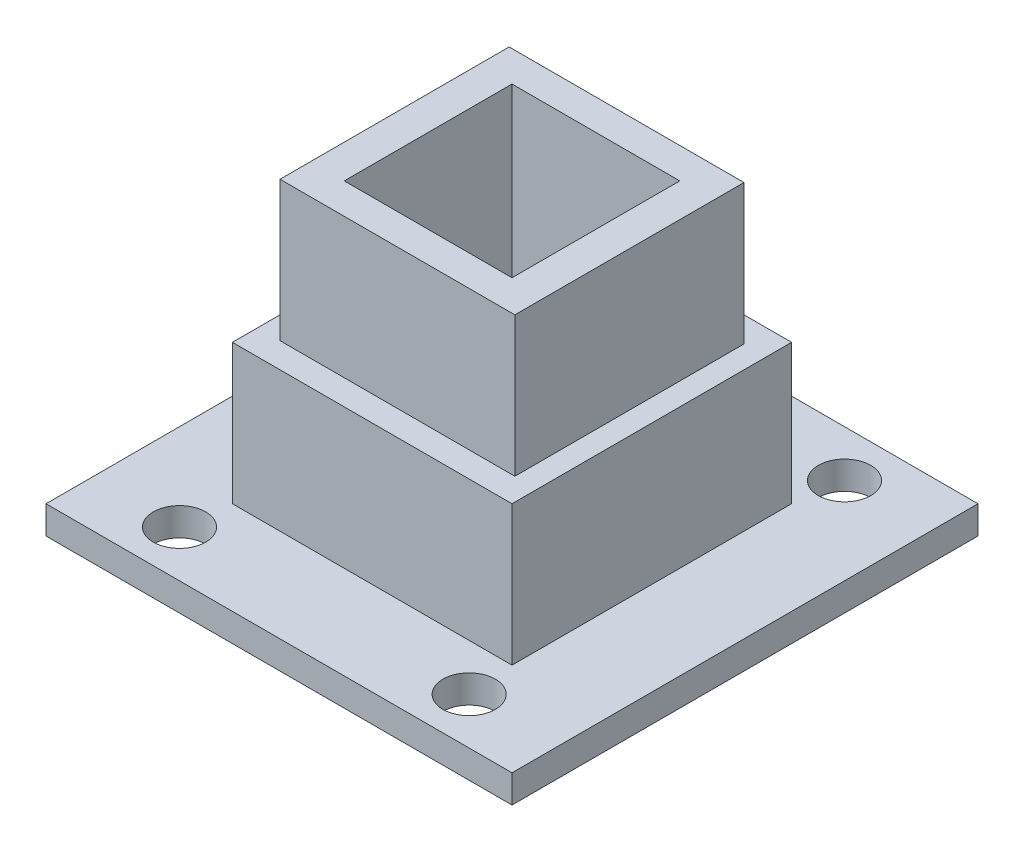
SolidWorks part; units mm, degrees
ref_plane "Alzado" through (0, 0, 0) normal (0, 0, 1) x (1, 0, 0)
ref_plane "Planta" through (0, 0, 0) normal (0, 1, 0) x (1, 0, 0)
ref_plane "Vista lateral" through (0, 0, 0) normal (1, 0, 0) x (0, 0, -1)
sketch "Croquis1" plane through (0, 0, 0) normal (0, 1, 0) x (1, 0, 0)
  line L1 (-25, 25) -> (25, 25)
  line L2 (-25, 25) -> (-25, -25)
  line L3 (-25, -25) -> (25, -25)
  line L4 (25, 25) -> (25, -25)
  line L5 (-25, 25) -> (25, -25) construction
  line L6 (-25, -25) -> (25, 25) construction
  point P0 (0, 0)
  dimension "D1" = 50
  dimension "D2" = 50
extrude "Saliente-Extruir1" add sketch "Croquis1" along normal blind 3
sketch "Croquis2" plane through (0, 3, 0) normal (0, 1, 0) x (1, 0, 0)
  line L1 (-15, 15) -> (15, 15)
  line L2 (-15, 15) -> (-15, -15)
  line L3 (-15, -15) -> (15, -15)
  line L4 (15, 15) -> (15, -15)
  line L5 (-15, 15) -> (15, -15) construction
  line L6 (-15, -15) -> (15, 15) construction
  line L7 (-9, 9) -> (9, 9)
  line L8 (-9, 9) -> (-9, -9)
  line L9 (-9, -9) -> (9, -9)
  line L10 (9, 9) -> (9, -9)
  line L11 (-9, 9) -> (9, -9) construction
  line L12 (-9, -9) -> (9, 9) construction
  point P0 (0, 0)
  point P6 (0, 0)
  dimension "D1" = 30
  dimension "D2" = 30
  dimension "D3" = 6
extrude "Saliente-Extruir2" add sketch "Croquis2" along normal blind 30
sketch "Croquis3" plane through (0, 3, 0) normal (0, 1, 0) x (1, 0, 0)
  line L0 (25, -20) -> (-25, -20) construction
  line L1 (25, -25) -> (25, 25) construction
  line L2 (-25, 25) -> (-25, -25) construction
  line L3 (25, 20) -> (-25, 20) construction
  line L4 (0, -25) -> (0, -15) construction
  line L5 (-25, -25) -> (25, -25) construction
  line L6 (-15, -15) -> (15, -15) construction
  line L7 (0, 15) -> (0, 25) construction
  line L8 (15, 15) -> (-15, 15) construction
  line L9 (25, 25) -> (-25, 25) construction
  line L10 (15.6762, -25) -> (15.6762, 25) construction
  line L11 (-15.6762, -25) -> (-15.6762, 25) construction
  circle A0 centre (15.4054, -20) radius 2.8139
  circle A1 centre (-15.6762, -20) radius 2.8139
  circle A2 centre (15.6762, 20) radius 2.8139
  circle A3 centre (-15.6762, 20) radius 2.8139
  point P22 (0, -20)
  point P29 (0, 20)
extrude "Cortar-Extruir1" cut sketch "Croquis3" against normal blind 10
sketch "Croquis4" plane through (0, 33, 0) normal (0, 1, 0) x (1, 0, 0)
  line L0 (-9, 9) -> (-9, -9) construction
  line L1 (15, -15) -> (-15, -15)
  line L2 (15, -15) -> (15, 15)
  line L3 (15, 15) -> (-15, 15)
  line L4 (-15, -15) -> (-15, 15)
  line L5 (12.6, -12.2932) -> (-12.6, -12.2932)
  line L6 (12.6, -12.2932) -> (12.6, 12.2932)
  line L7 (12.6, 12.2932) -> (-12.6, 12.2932)
  line L8 (-12.6, -12.2932) -> (-12.6, 12.2932)
  line L9 (12.6, -12.2932) -> (-12.6, 12.2932) construction
  line L10 (12.6, 12.2932) -> (-12.6, -12.2932) construction
  point P6 (0, 0)
  dimension "D1" = 3.6
extrude "Cortar-Extruir2" cut sketch "Croquis4" against normal blind 15
